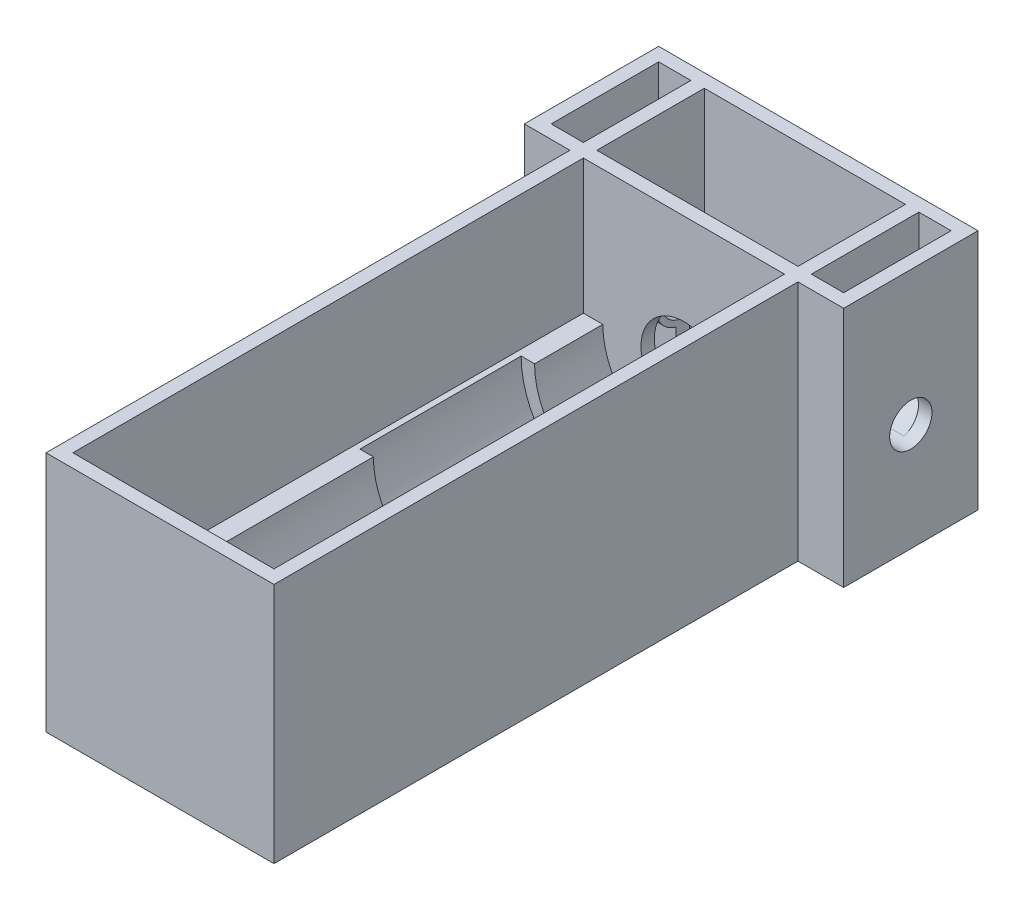
SolidWorks part; units mm, degrees
ref_plane "Front Plane" through (0, 0, 0) normal (0, 0, 1) x (1, 0, 0)
ref_plane "Top Plane" through (0, 0, 0) normal (0, 1, 0) x (1, 0, 0)
ref_plane "Right Plane" through (0, 0, 0) normal (1, 0, 0) x (0, 0, -1)
sketch "Sketch1" plane through (0, 0, 0) normal (0, 0, 1) x (1, 0, 0)
  line L1 (-26.9397, 0) -> (26.9397, 0)
  line L2 (-26.9397, 0) -> (-26.9397, 6.35)
  line L3 (-23.7647, 6.35) -> (23.7647, 6.35)
  line L4 (26.9397, 0) -> (26.9397, 6.35)
  line L6 (-26.9397, 6.35) -> (-26.9397, 57.15)
  line L7 (-26.9397, 57.15) -> (-23.7647, 57.15)
  line L8 (-23.7647, 6.35) -> (-23.7647, 57.15)
  line L10 (26.9397, 6.35) -> (26.9397, 57.15)
  line L11 (26.9397, 57.15) -> (23.7647, 57.15)
  line L12 (23.7647, 6.35) -> (23.7647, 57.15)
  dimension "D1" = 3.175
  dimension "D2" = 53.8795
  dimension "D3" = 6.35
  dimension "D4" = 50.8
extrude "Boss-Extrude1" add sketch "Sketch1" along normal mid plane 25.4
sketch "Sketch2" plane through (0, 0, -12.7) normal (0, 0, -1) x (-1, 0, 0)
  line L0 (26.9397, 0) -> (-26.9397, 0) construction
  line L1 (-26.9397, 57.15) -> (26.9397, 57.15)
  line L2 (-26.9397, 57.15) -> (-26.9397, 0)
  line L3 (-26.9397, 0) -> (26.9397, 0)
  line L4 (26.9397, 57.15) -> (26.9397, 0)
extrude "Boss-Extrude2" add sketch "Sketch2" along normal blind 3.175
sketch "Sketch6" plane through (0, 0, 0) normal (0, 0, 1) x (1, 0, 0)
  line L0 (-23.7647, 25.4) -> (-16.1447, 25.4)
  line L3 (-16.1447, 25.4) -> (-16.1447, 31.75)
  line L4 (-16.1447, 31.75) -> (-21.2247, 31.75)
  line L5 (-21.2247, 31.75) -> (-23.7647, 33.02)
  line L6 (0, 25.4) -> (0, 0) construction
  line L7 (-23.7647, 33.02) -> (-23.7647, 25.4)
  line L9 (-23.7647, 6.35) -> (-23.7647, 57.15) construction
  line L10 (23.7647, 33.02) -> (23.7647, 25.4)
  line L11 (21.2247, 31.75) -> (23.7647, 33.02)
  line L12 (16.1447, 31.75) -> (21.2247, 31.75)
  line L13 (16.1447, 25.4) -> (16.1447, 31.75)
  line L15 (23.7647, 25.4) -> (16.1447, 25.4)
  dimension "D1" = 6.35
  dimension "D2" = 5.08
  dimension "D3" = 7.62
  dimension "D4" = 7.62
  dimension "D5" = 25.4
revolve "Revolve2" add sketch "Sketch6" angle 360 about L0
sketch "Sketch3" plane through (0, 0, 0) normal (1, 0, 0) x (0, 0, -1)
  circle A0 centre (0, 25.4) radius 5
  circle A1 centre (0, 25.4) radius 6.35 construction
  dimension "D2" = 10
extrude "Cut-Extrude2" cut sketch "Sketch3" against normal through all both and the other way through all
sketch "Sketch5" plane through (0, 0, 0) normal (0, -1, 0) x (1, 0, 0)
  line L1 (26.9397, -15.875) -> (-26.9397, -15.875)
  line L2 (26.9397, -15.875) -> (26.9397, -41.275)
  line L3 (26.9397, -41.275) -> (-26.9397, -41.275)
  line L4 (-26.9397, -15.875) -> (-26.9397, -41.275)
  circle A0 centre (7.8897, -28.575) radius 3.4925
  circle A1 centre (-17.5103, -28.575) radius 3.4925
  point P9 (26.9397, -28.575)
  dimension "D2" = 6.985
  dimension "D1" = 25.4
  dimension "D3" = 19.05
  dimension "D4" = 2
extrude "Boss-Extrude3" add sketch "Sketch5" against normal blind 6.35
sketch "Sketch7" plane through (0, 0, 0) normal (0, 0, 1) x (1, 0, 0)
  line L0 (23.7647, 6.35) -> (-23.7647, 6.35) construction
  line L1 (-23.7647, 21.9594) -> (-16.1447, 21.9594)
  line L2 (-23.7647, 21.9594) -> (-23.7647, 6.35)
  line L3 (-23.7647, 6.35) -> (-16.1447, 6.35)
  line L4 (-16.1447, 21.9594) -> (-16.1447, 6.35)
  line L5 (-23.7647, 21.9594) -> (-16.1447, 6.35) construction
  line L6 (-23.7647, 6.35) -> (-16.1447, 21.9594) construction
  line L8 (0, 0) -> (0, 25.6446) construction
  line L9 (-26.9397, 0) -> (26.9397, 0) construction
  line L10 (23.7647, 6.35) -> (16.1447, 21.9594) construction
  line L11 (23.7647, 21.9594) -> (16.1447, 6.35) construction
  line L12 (16.1447, 21.9594) -> (16.1447, 6.35)
  line L13 (23.7647, 6.35) -> (16.1447, 6.35)
  line L14 (23.7647, 21.9594) -> (23.7647, 6.35)
  line L15 (23.7647, 21.9594) -> (16.1447, 21.9594)
  line L16 (-23.7647, 6.35) -> (-23.7647, 57.15) construction
  line L17 (-16.1447, 19.05) -> (-16.1447, 31.75) construction
  point P4 (-19.9547, 14.1547)
  point P18 (19.9547, 14.1547)
extrude "Boss-Extrude7" add sketch "Sketch7" along normal mid plane 3.175
sketch "Sketch8" plane through (0, 0, 12.7) normal (0, 0, 1) x (1, 0, 0)
  line L1 (-26.9397, 57.15) -> (26.9397, 57.15)
  line L2 (-26.9397, 57.15) -> (-26.9397, 0)
  line L3 (-26.9397, 0) -> (26.9397, 0)
  line L4 (26.9397, 57.15) -> (26.9397, 0)
  line L5 (-26.9397, 57.15) -> (26.9397, 0) construction
  line L6 (-26.9397, 0) -> (26.9397, 57.15) construction
  point P4 (0, 28.575)
extrude "Boss-Extrude8" add sketch "Sketch8" along normal blind 127
sketch "Sketch9" plane through (0, 0, 0) normal (1, 0, 0) x (0, 0, -1)
  line L0 (0, 25.4) -> (-139.7, 25.4) construction
  line L1 (-139.7, 0) -> (-139.7, 57.15) construction
  line L2 (-70.104, 47.752) -> (-70.104, 44.577)
  line L3 (-70.104, 47.752) -> (-32.004, 47.752)
  line L4 (-32.004, 47.752) -> (-32.004, 44.577)
  line L5 (-32.004, 44.577) -> (-20.1041, 44.577)
  line L6 (0, 35.56) -> (0, 25.4)
  line L7 (0, 25.4) -> (12.7, 25.4) construction
  line L8 (12.7, 6.35) -> (12.7, 57.15) construction
  line L9 (0, 25.4) -> (-70.104, 25.4)
  line L10 (-70.104, 44.577) -> (-136.525, 44.577)
  line L11 (-136.525, 44.577) -> (-136.525, 25.4)
  line L12 (-136.525, 25.4) -> (-70.104, 25.4)
  line L13 (-20.1041, 44.577) -> (-20.1041, 35.56)
  line L14 (-20.1041, 35.56) -> (0, 35.56)
  dimension "D1" = 38.1
  dimension "D2" = 10.16
  dimension "D3" = 22.352
  dimension "D4" = 3.175
  dimension "D5" = 3.175
revolve "Cut-Revolve1" cut sketch "Sketch9" angle 360 about L9
ref_axis "Axis2" through (0, 25.4, 70.104) along (0, 0, -1)
ref_axis "Axis3" through (-26.9397, 25.4, 0) along (1, 0, 0)
ref_plane "Plane2" through (0, 25.4, 0) normal (0, -1, 0) x (-1, 0, 0)
sketch "Sketch13" plane through (0, 0, 0) normal (0, -1, 0) x (-1, 0, 0)
  line L0 (26.9397, -139.7) -> (26.9397, 41.275) construction
  line L1 (26.9397, -15.4709) -> (26.9421, -15.4709)
  line L2 (26.9397, -15.4709) -> (26.9397, -139.7)
  line L3 (26.9397, -139.7) -> (26.9421, -139.7)
  line L4 (26.9421, -15.4709) -> (26.9421, -139.7)
  line L5 (26.9397, -15.4709) -> (26.9421, -139.7) construction
  line L6 (26.9397, -139.7) -> (26.9421, -15.4709) construction
  line L7 (26.9397, -139.7) -> (-26.9397, -139.7) construction
  line L9 (-26.9397, -139.7) -> (-26.9374, -139.7)
  line L10 (-26.9397, -139.7) -> (-26.9397, -15.4709)
  line L11 (-26.9397, -15.4709) -> (-26.9374, -15.4709)
  line L12 (-26.9374, -139.7) -> (-26.9374, -15.4709)
  line L13 (-26.9397, -139.7) -> (-26.9374, -15.4709) construction
  line L14 (-26.9397, -15.4709) -> (-26.9374, -139.7) construction
  point P4 (26.9409, -77.5855)
  point P13 (-26.9386, -77.5855)
extrude "Cut-Extrude7" cut sketch "Sketch13" against normal through all both and the other way through all
sketch "Sketch14" plane through (0, 57.15, 0) normal (0, 1, 0) x (1, 0, 0)
  line L1 (23.7624, -136.525) -> (-23.7647, -136.525)
  line L2 (23.7624, -136.525) -> (23.7624, -15.875)
  line L3 (23.7624, -15.875) -> (-23.7647, -15.875)
  line L4 (-23.7647, -136.525) -> (-23.7647, -15.875)
  line L5 (23.7624, -136.525) -> (-23.7647, -15.875) construction
  line L6 (23.7624, -15.875) -> (-23.7647, -136.525) construction
  line L7 (26.9374, -139.7) -> (-26.9397, -139.7) construction
  line L8 (26.9374, -139.7) -> (26.9374, -15.4709) construction
  line L10 (23.7647, -12.7) -> (-23.7647, -12.7) construction
  line L11 (-26.9397, -139.7) -> (-26.9397, 15.875) construction
  point P4 (-0.0012, -76.2)
  dimension "D1" = 3.175
  dimension "D2" = 3.175
  dimension "D3" = 3.175
  dimension "D4" = 3.175
extrude "Cut-Extrude8" cut sketch "Sketch14" against normal up to surface (31.75 mm away) up to plane "Plane2"
sketch "Sketch15" plane through (0, 0, 20.1041) normal (0, 0, 1) x (1, 0, 0)
  line L2 (-10.16, 25.4) -> (-19.177, 25.4)
  line L3 (19.177, 25.4) -> (10.16, 25.4)
  line L4 (-10.16, 25.4) -> (-19.177, 25.4)
  line L5 (19.177, 25.4) -> (10.16, 25.4)
  arc A2 (-19.177, 25.4) -> (19.177, 25.4) centre (0, 25.4) ccw
  arc A3 (-10.16, 25.4) -> (10.16, 25.4) centre (0, 25.4) ccw
  arc A4 (-19.177, 25.4) -> (19.177, 25.4) centre (0, 25.4) ccw
  arc A5 (-10.16, 25.4) -> (10.16, 25.4) centre (0, 25.4) ccw
  dimension "D1" = 0
extrude "Cut-Extrude9" cut sketch "Sketch15" against normal up to surface (4.2291 mm away) up to face at (-0.0008, 37.6767, 15.875)
sketch "Sketch16" plane through (0, 6.35, 0) normal (0, 1, 0) x (1, 0, 0)
  line L1 (26.9397, 41.275) -> (-26.9397, 41.275)
  line L2 (26.9397, 41.275) -> (26.9397, 15.875)
  line L3 (26.9397, 15.875) -> (-26.9397, 15.875)
  line L4 (-26.9397, 41.275) -> (-26.9397, 15.875)
  line L5 (26.9397, 41.275) -> (-26.9397, 15.875) construction
  line L6 (26.9397, 15.875) -> (-26.9397, 41.275) construction
  point P4 (0, 28.575)
extrude "Cut-Extrude10" cut sketch "Sketch16" against normal through all
sketch "Sketch18" plane through (0, 0, 0) normal (0, 1, 0) x (1, 0, 0)
  line L0 (-26.9397, 15.875) -> (26.9397, 15.875) construction
  line L1 (-23.7647, 15.875) -> (-37.7347, 15.875)
  line L2 (-23.7647, 15.875) -> (-23.7647, -15.875)
  line L3 (-23.7647, -15.875) -> (-37.7347, -15.875)
  line L4 (-37.7347, 15.875) -> (-37.7347, -15.875)
  line L5 (-23.7647, 15.875) -> (-37.7347, -15.875) construction
  line L6 (-23.7647, -15.875) -> (-37.7347, 15.875) construction
  line L7 (-23.7647, -12.7) -> (-23.7647, 12.7) construction
  line L8 (-19.177, -15.875) -> (-23.7647, -15.875) construction
  line L9 (-26.9397, -139.7) -> (-26.9397, 15.875) construction
  line L10 (-34.5597, 12.7) -> (-26.9397, 12.7)
  line L11 (-34.5597, 12.7) -> (-34.5597, -12.7)
  line L12 (-34.5597, -12.7) -> (-26.9397, -12.7)
  line L13 (-26.9397, 12.7) -> (-26.9397, -12.7)
  line L14 (-34.5597, 12.7) -> (-26.9397, -12.7) construction
  line L15 (-34.5597, -12.7) -> (-26.9397, 12.7) construction
  point P4 (-30.7497, 0)
  point P15 (-30.7497, 0)
  dimension "D1" = 7.62
  dimension "D2" = 3.175
  dimension "D3" = 3.175
extrude "Boss-Extrude10" add sketch "Sketch18" along normal up to surface (57.15 mm away) up to face at (-0.0012, 57.15, 76.2)
sketch "Sketch19" plane through (0, 0, 0) normal (1, 0, 0) x (0, 0, -1)
  line L0 (1.5875, 20.6587) -> (12.7, 24.3794)
  line L1 (12.7, 6.35) -> (12.7, 57.15) construction
  line L2 (-1.5875, 20.6587) -> (-12.7, 24.3794)
  line L3 (-12.7, 15.24) -> (-12.7, 35.56) construction
  line L4 (-12.7, 24.3794) -> (-12.7, 0)
  line L5 (-12.7, 0) -> (12.7, 0)
  line L6 (12.7, 0) -> (12.7, 24.3794)
  arc A0 (-1.5875, 20.6587) -> (1.5875, 20.6587) centre (0, 25.4) ccw
  circle A1 centre (0, 25.4) radius 5 construction
  dimension "D1" = 3.175
extrude "Boss-Extrude11" add sketch "Sketch19" against normal up to next from surface starting at face at (-26.9397, 28.575, 0)
mirror "Mirror4" about plane through (0, 0, 0) normal (1, 0, 0) of "Boss-Extrude10"
extrude "Boss-Extrude12" add sketch "Sketch19<2>" along normal up to next from surface starting at face at (26.9397, 28.575, 0)
sketch "Sketch19<2>" plane through (0, 0, 0) normal (1, 0, 0) x (0, 0, -1) same geometry as "Sketch19"
sketch "Sketch20" plane through (-23.7647, 0, 0) normal (1, 0, 0) x (0, 0, -1)
  circle A0 centre (0, 25.4) radius 5 construction
  circle A1 centre (0, 25.4) radius 5
extrude "Cut-Extrude11" cut sketch "Sketch20" against normal through all both and the other way through all
